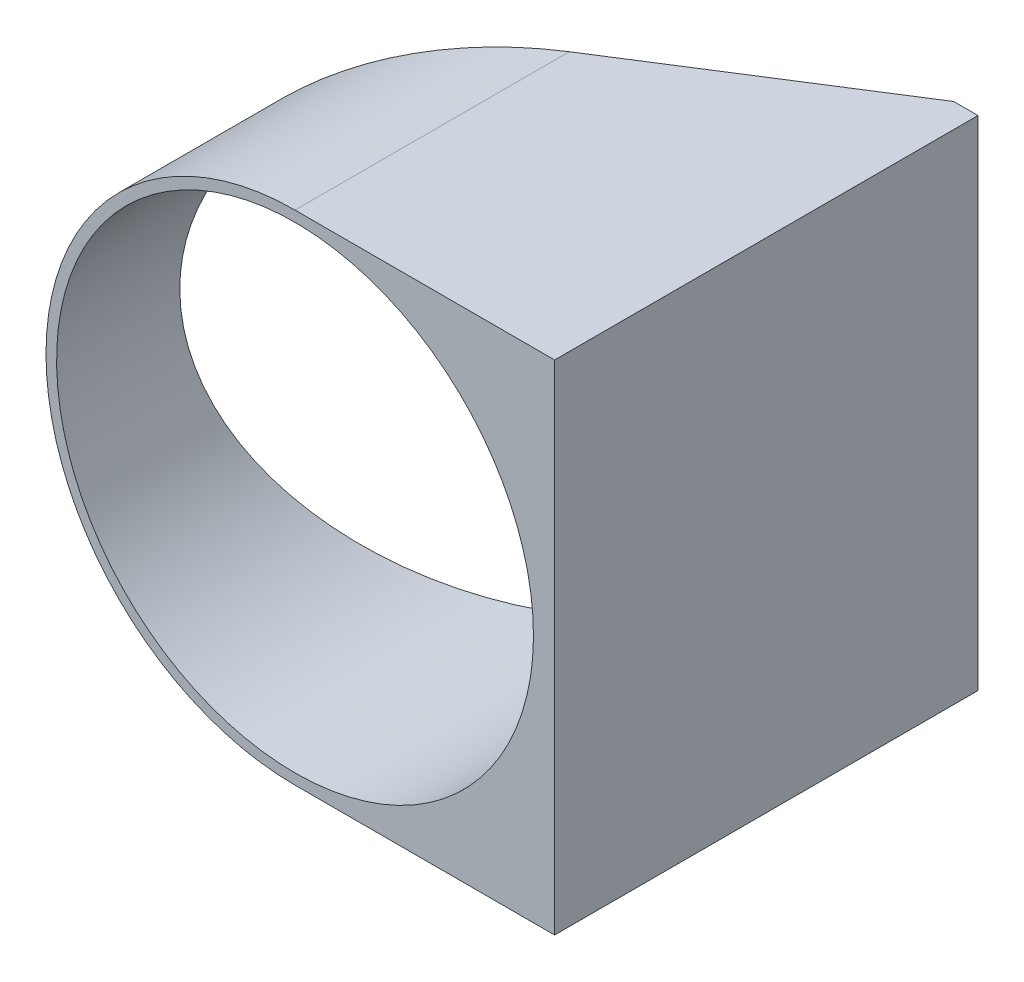
SolidWorks part; units mm, degrees
ref_plane "Front Plane" through (0, 0, 0) normal (0, 0, 1) x (1, 0, 0)
ref_plane "Top Plane" through (0, 0, 0) normal (0, 1, 0) x (1, 0, 0)
ref_plane "Right Plane" through (0, 0, 0) normal (1, 0, 0) x (0, 0, -1)
sketch "Sketch1" plane through (0, 0, 0) normal (0, 0, 1) x (1, 0, 0)
  circle A0 centre (443.1275, 0) radius 22.225 construction
  circle A1 centre (443.1275, 0) radius 22.225 construction
  circle A2 centre (443.1275, 0) radius 22.525
  circle A3 centre (443.1275, 0) radius 23.525
  dimension "D1" = 0.3
  dimension "D2" = 1.3
extrude "Boss-Extrude1" add sketch "Sketch1" along normal blind 40 from vertex
sketch "Sketch2" plane through (0, 0, -519.1927) normal (0, 0, 1) x (1, 0, 0)
  line L0 (443.1275, 23.525) -> (466.6525, 23.525)
  line L1 (466.6525, 23.525) -> (466.6525, 0)
  line L2 (466.6525, 0) -> (466.6525, -23.525)
  line L3 (466.6525, -23.525) -> (443.1275, -23.525)
  line L5 (466.6525, -23.525) -> (467.6525, -23.525)
  line L6 (466.6525, -23.525) -> (466.6525, 23.525)
  line L7 (466.6525, 23.525) -> (467.6525, 23.525)
  line L8 (467.6525, -23.525) -> (467.6525, 23.525)
  circle A0 centre (443.1275, 0) radius 23.525 construction
  circle M2 centre (443.1275, 0) radius 23.525
  dimension "D1" = 1
extrude "Boss-Extrude2" add sketch "Sketch2" against normal blind 40 contours L5 L8 L7 L1 L2 | L1 L0 M2 | L3 L2 M2
sketch "Sketch3" plane through (0, 0, 0) normal (0, 1, 0) x (1, 0, 0)
  line L0 (420.9025, 531.0194) -> (465.3525, 559.1927) construction
  line L1 (419.6025, 530.1954) -> (465.3525, 559.1927)
  line L2 (419.6025, 559.1927) -> (419.6025, 519.1927) construction
  line L4 (419.6025, 559.1927) -> (419.6025, 530.1954)
  line L5 (443.1275, 559.1927) -> (467.6525, 559.1927) construction
  line L6 (443.1275, 559.1927) -> (419.6025, 559.1927) construction
  line L7 (443.1275, 559.1927) -> (465.3525, 559.1927)
  line L8 (443.1275, 559.1927) -> (419.6025, 559.1927)
  point P2 (465.6525, 559.1927)
  point P5 (419.6025, 530.1729)
  point P9 (465.3343, 559.1927)
extrude "Cut-Extrude1" cut sketch "Sketch3" against normal through all both and the other way through all
